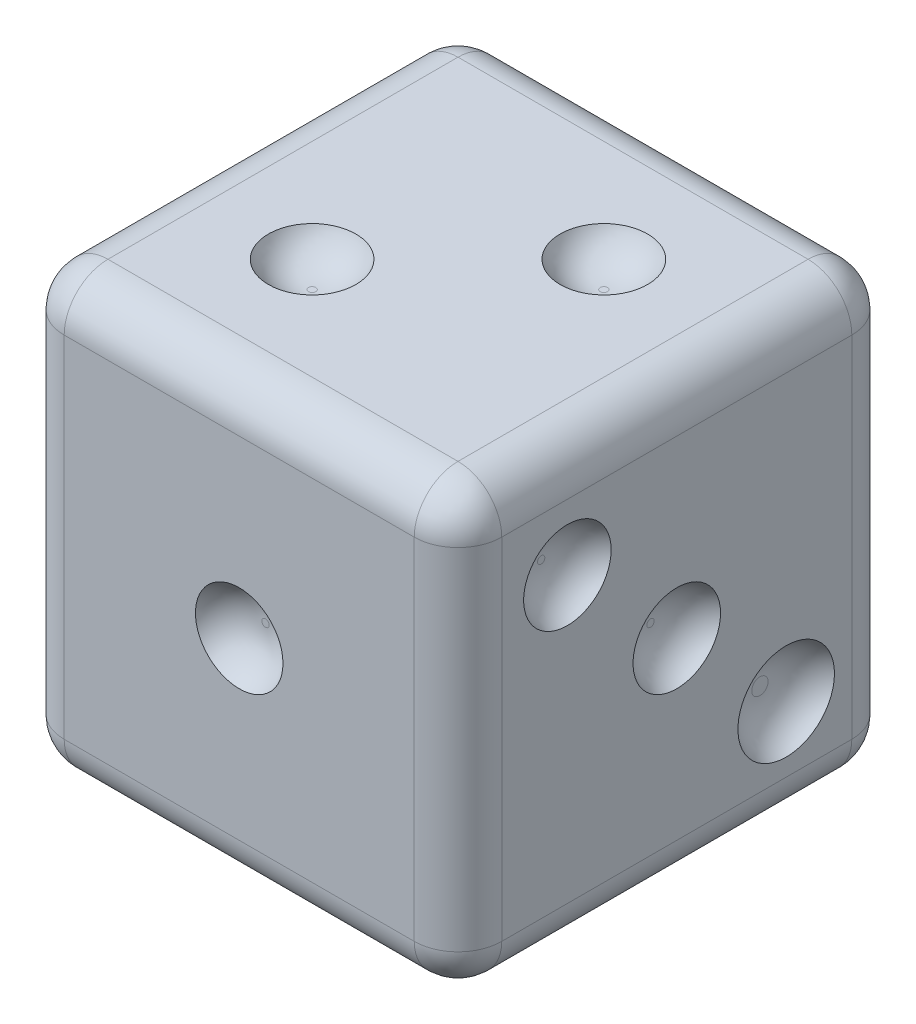
SolidWorks part; units mm, degrees
ref_plane "Front Plane" through (0, 0, 0) normal (1, 0, 0) x (0, 1, 0)
ref_plane "Top Plane" through (0, 0, 0) normal (0, 0, 1) x (0, 1, 0)
ref_plane "Right Plane" through (0, 0, 0) normal (0, 1, 0) x (-1, 0, 0)
sketch "Sketch3" plane through (0, 0, 0) normal (1, 0, 0) x (0, 1, 0)
  line L1 (-31.75, -31.75) -> (31.75, -31.75)
  line L2 (-31.75, -31.75) -> (-31.75, 31.75)
  line L3 (-31.75, 31.75) -> (31.75, 31.75)
  line L4 (31.75, -31.75) -> (31.75, 31.75)
  line L5 (-31.75, -31.75) -> (31.75, 31.75) construction
  line L6 (-31.75, 31.75) -> (31.75, -31.75) construction
  point P0 (0, 0)
  point P6 (-31.75, 31.75)
  dimension "D1" = 63.5
  dimension "D2" = 63.5
extrude "Boss-Extrude2" add sketch "Sketch3" along normal blind 63.5 contours L3 L4 L1 L2
fillet "Fillet1" radius 6.35 12 edges at (63.5, 0, 31.75) (63.5, 31.75, 0) (31.75, 31.75, 31.75) (0, 31.75, 0) (0, 0, 31.75) (31.75, -31.75, 31.75) (63.5, -31.75, 0) (0, -31.75, 0) (31.75, -31.75, -31.75) (63.5, 0, -31.75) (31.75, 31.75, -31.75) (0, 0, -31.75)
sketch "Sketch4" plane through (0, 0, 31.75) normal (0, 0, 1) x (1, 0, 0)
  line L0 (6.35, 0) -> (57.15, 0) construction
  line L1 (6.35, 25.4) -> (6.35, -25.4) construction
  line L2 (57.15, -25.4) -> (57.15, 25.4) construction
  circle A0 centre (31.75, 0) radius 6.35
  dimension "D1" = 12.7
extrude "Cut-Extrude2" cut sketch "Sketch4" against normal blind 3.81 contours A0
fillet "Fillet2" radius 6.35 1 edges at (38.1, 0, 27.94)
sketch "Sketch6" plane through (63.5, 0, 0) normal (1, 0, 0) x (0, 1, 0)
  line L0 (25.4, 25.4) -> (-25.4, -25.4) construction
  line L1 (25.4, 25.4) -> (-25.4, 25.4) construction
  line L2 (-25.4, -25.4) -> (25.4, -25.4) construction
  circle A0 centre (0, 0) radius 6.35
  circle A1 centre (15.875, 15.875) radius 6.35
  circle A2 centre (-15.875, -15.875) radius 7.0048
  point P11 (0, 0)
  dimension "D1" = 12.7
  dimension "D2" = 12.7
  dimension "D3" = 14.0096
  dimension "D4" = 9.525
  dimension "D5" = 9.525
extrude "Cut-Extrude3" cut sketch "Sketch6" against normal blind 3.81 contours A2 | A0 | A1
fillet "Fillet3" radius 6.35 3 edges at (59.69, 15.875, 9.525) (59.69, 0, -6.35) (59.69, -15.875, -22.8798)
sketch "Sketch7" plane through (0, 31.75, 0) normal (0, 1, 0) x (-1, 0, 0)
  line L0 (-6.35, 25.4) -> (-57.15, -25.4) construction
  line L1 (-6.35, 25.4) -> (-57.15, 25.4) construction
  line L2 (-57.15, -25.4) -> (-6.35, -25.4) construction
  circle A0 centre (-21.1658, 10.5842) radius 6.35
  circle A1 centre (-42.3342, -10.5842) radius 6.35
  dimension "D1" = 12.7
  dimension "D2" = 12.7
  dimension "D3" = 14.8158
  dimension "D4" = 14.8158
extrude "Cut-Extrude4" cut sketch "Sketch7" against normal blind 3.81 contours A1 | A0
fillet "Fillet4" radius 6.35 2 edges at (42.3342, 27.94, -4.2342) (21.1658, 27.94, 16.9342)
sketch "Sketch8" plane through (0, -31.75, 0) normal (0, -1, 0) x (1, 0, 0)
  line L0 (31.75, 25.4) -> (31.75, -25.4) construction
  line L1 (57.15, 25.4) -> (6.35, 25.4) construction
  line L2 (6.35, -25.4) -> (57.15, -25.4) construction
  line L3 (6.35, 0) -> (57.15, 0) construction
  line L4 (6.35, 25.4) -> (6.35, -25.4) construction
  line L5 (57.15, -25.4) -> (57.15, 25.4) construction
  circle A0 centre (19.05, 12.7) radius 6.35
  circle A1 centre (44.45, 12.7) radius 6.35
  circle A2 centre (44.45, -12.7) radius 6.35
  circle A3 centre (19.05, -12.7) radius 6.35
  dimension "D1" = 12.7
  dimension "D2" = 12.7
  dimension "D3" = 12.7
extrude "Cut-Extrude5" cut sketch "Sketch8" against normal blind 3.81 contours A1 | A0 | A3 | A2
fillet "Fillet5" radius 6.35 4 edges at (44.45, -27.94, 19.05) (19.05, -27.94, 6.35) (19.05, -27.94, -6.35) (44.45, -27.94, -19.05)
sketch "Sketch9" plane through (0, 0, 0) normal (-1, 0, 0) x (0, -1, 0)
  line L0 (25.4, -25.4) -> (25.4, 25.4) construction
  line L1 (-25.4, 0) -> (25.4, 0) construction
  line L2 (25.4, 25.4) -> (-25.4, 25.4) construction
  line L3 (-25.4, 25.4) -> (-25.4, -25.4) construction
  line L4 (0, 25.4) -> (0, -25.4) construction
  line L5 (-25.4, -25.4) -> (25.4, -25.4) construction
  circle A0 centre (0, 0) radius 6.35
  circle A2 centre (15.875, 15.875) radius 6.35
  circle A5 centre (-15.875, 15.875) radius 6.35
  circle A6 centre (15.875, -15.875) radius 6.35
  circle A7 centre (-15.875, -15.875) radius 6.35
  dimension "D1" = 12.7
  dimension "D4" = 12.7
  dimension "D6" = 9.525
  dimension "D7" = 9.525
extrude "Cut-Extrude6" cut sketch "Sketch9" against normal blind 3.81 contours A0 | A2 | A7 | A6 | A5
fillet "Fillet6" radius 6.35 5 edges at (3.81, -15.875, -22.225) (3.81, 15.875, -9.525) (3.81, 0, 6.35) (3.81, -15.875, 22.225) (3.81, 15.875, 9.525)
sketch "Sketch10" plane through (0, 0, -31.75) normal (0, 0, -1) x (1, 0, 0)
  line L0 (6.35, -12.7) -> (57.15, -12.7) construction
  line L1 (6.35, 25.4) -> (6.35, -25.4) construction
  line L2 (57.15, -25.4) -> (57.15, 25.4) construction
  line L3 (6.35, -25.4) -> (57.15, -25.4) construction
  line L4 (6.35, 0) -> (57.15, 0) construction
  circle A0 centre (31.75, -12.7) radius 6.35
  circle A1 centre (15.875, -12.7) radius 6.35
  circle A2 centre (47.625, -12.7) radius 6.35
  circle A3 centre (47.625, 12.7) radius 6.35
  circle A4 centre (31.75, 12.7) radius 6.35
  circle A5 centre (15.875, 12.7) radius 6.35
  dimension "D2" = 12.7
  dimension "D3" = 12.7
  dimension "D4" = 12.7
  dimension "D1" = 12.7
  dimension "D5" = 9.525
  dimension "D6" = 9.525
extrude "Cut-Extrude7" cut sketch "Sketch10" against normal blind 3.81 contours A1 | A0 | A5 | A4 | A2 | A3
fillet "Fillet7" radius 6.35 6 edges at (9.525, 12.7, -27.94) (22.225, -12.7, -27.94) (38.1, -12.7, -27.94) (25.4, 12.7, -27.94) (41.275, 12.7, -27.94) (53.975, -12.7, -27.94)
